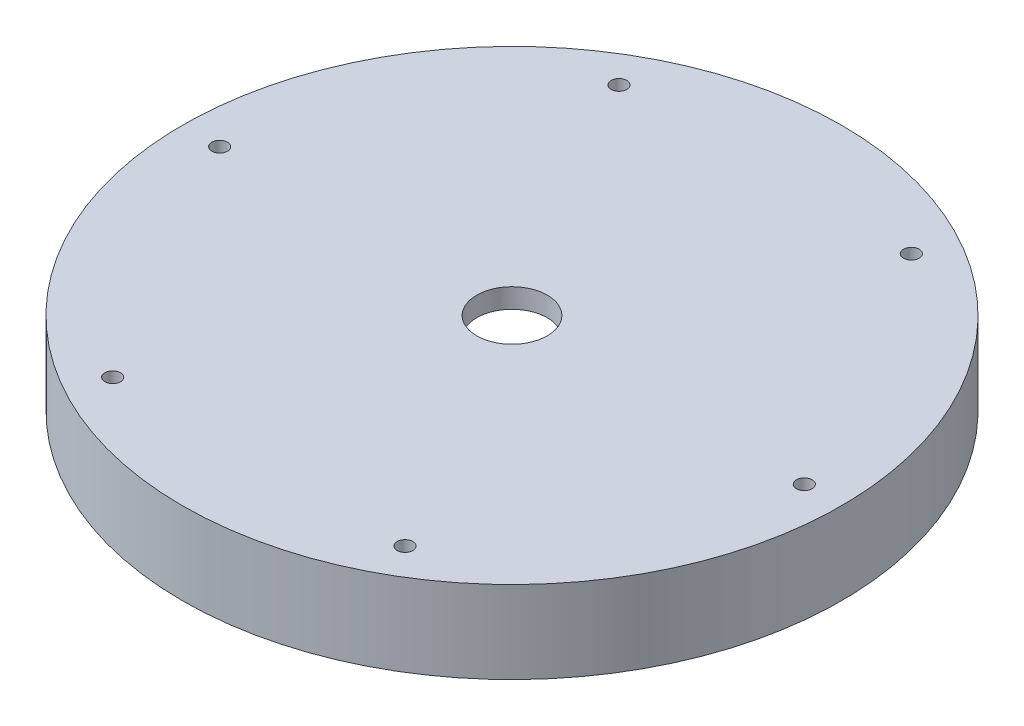
SolidWorks part; units mm, degrees
material "1060 Alloy"
ref_plane "Front Plane" through (0, 0, 0) normal (0, 0, 1) x (1, 0, 0)
ref_plane "Top Plane" through (0, 0, 0) normal (0, 1, 0) x (1, 0, 0)
ref_plane "Right Plane" through (0, 0, 0) normal (1, 0, 0) x (0, 0, -1)
sketch "Sketch1" plane through (0, 0, 0) normal (0, 0, 1) x (1, 0, 0)
  line L0 (0, 38.7087) -> (0, -19.5852) construction
  line L1 (-4.5, 0) -> (-42.0375, 0)
  line L2 (-42.0375, 0) -> (-42.0375, -10.5)
  line L4 (-20, -11.75) -> (-20, -2.5)
  line L5 (-20, -2.5) -> (-4.5, -2.5)
  line L6 (-4.5, -2.5) -> (-4.5, 0)
  line L7 (-20, -11.75) -> (-39.0375, -11.75)
  line L8 (-39.0375, -11.75) -> (-39.0375, -10.5)
  line L9 (-39.0375, -10.5) -> (-42.0375, -10.5)
  point P5 (-39.0375, -29.2743)
  dimension "D1" = 4.5
  dimension "D2" = 20
  dimension "D4" = 42.0375
  dimension "D5" = 3
  dimension "D6" = 1.25
  dimension "D7" = 2.5
  dimension "D3" = 8
revolve "Revolve1" add sketch "Sketch1" angle 360 about L0
sketch "Sketch2" plane through (0, -11.75, 0) normal (0, -1, 0) x (1, 0, 0)
  circle A0 centre (0, 0) radius 37.2875 construction
  circle A1 centre (-37.2875, 0) radius 1
  circle A2 centre (-18.6438, 32.2919) radius 1
  circle A3 centre (18.6438, 32.2919) radius 1
  circle A4 centre (37.2875, 0) radius 1
  circle A5 centre (18.6438, -32.2919) radius 1
  circle A6 centre (-18.6437, -32.2919) radius 1
  point P6 (0, 0)
  point P7 (0, 0)
  point P17 (0, 0)
  dimension "D1" = 2
  dimension "D3" = 74.575
  dimension "D2" = 6
extrude "Cut-Extrude1" cut sketch "Sketch2" against normal through all
equation "\"Stator_OD\"= 68'No Tolerance given"
equation "\"A\"=18.34 'taken off spec sheet for 06808 (A)"
equation "\"Rotor_ID\"= 34'No Tolerance Given"
equation "\"back_bearing_Thickness\"= 8'randomish, thinnest off mcmaster"
equation "\"back_bearing_OD\"= 25'currently non-sense"
equation "\"Stator_Gap\"= 0.0375'+- 0.0125 (From 1.3.3.1 Kollmorgen manual)"
equation "\"Back_mount_hole\"= 1.75'To be tapped to M2 (USE LOCKTITE)"
equation "\"facePlate_Mount_Hole\"= 5.75'To be tapped to M6"
equation "\"back_bearing_ID\"= 15'Random number"
equation "\"final_shaftD\"= 8'NEMA 23 shaft diameter. Should fit with harmonic?"
equation "\"final_shaftL\"= 50'random length. Idk"
equation "\"back_bearing_IDOD\"= 18'Random number, OD of the inner bearing ring"
equation "\"rotor_shaftD\"= \"Rotor_ID\" - (0.0185)*2'+-0.0065 (from manual)"
equation "\"front_bearing_ID\"= 12'random"
equation "\"front_bearing_OD\"= 20'random"
equation "\"front_bearing_IDOD\"= 14'random"
equation "\"front_bearing_Thickness\"= 5'randomish, thinnest off mcmaster"
equation "\"rotor_thickness\"= 2.4'measured off CAD"
equation "\"rotor_height\"= 14.76'+-0.08 taken off spec sheet for 06808 (C)"
equation "\"D1@Sketch1\"=\"final_shaftD\"/2+0.5"
equation "\"D2@Sketch1\"=\"front_bearing_OD\""
equation "\"D4@Sketch1\"=\"Stator_OD\"/2+\"Stator_Gap\"+8"
equation "\"D3@Sketch1\"=\"front_bearing_Thickness\"+3"
equation "\"D3@Sketch2\"= \"Stator_OD\" + \"Stator_Gap\" * 2 + 6.5"
equation "\"D1@Sketch2\"=\"Back_mount_hole\"+0.25"
